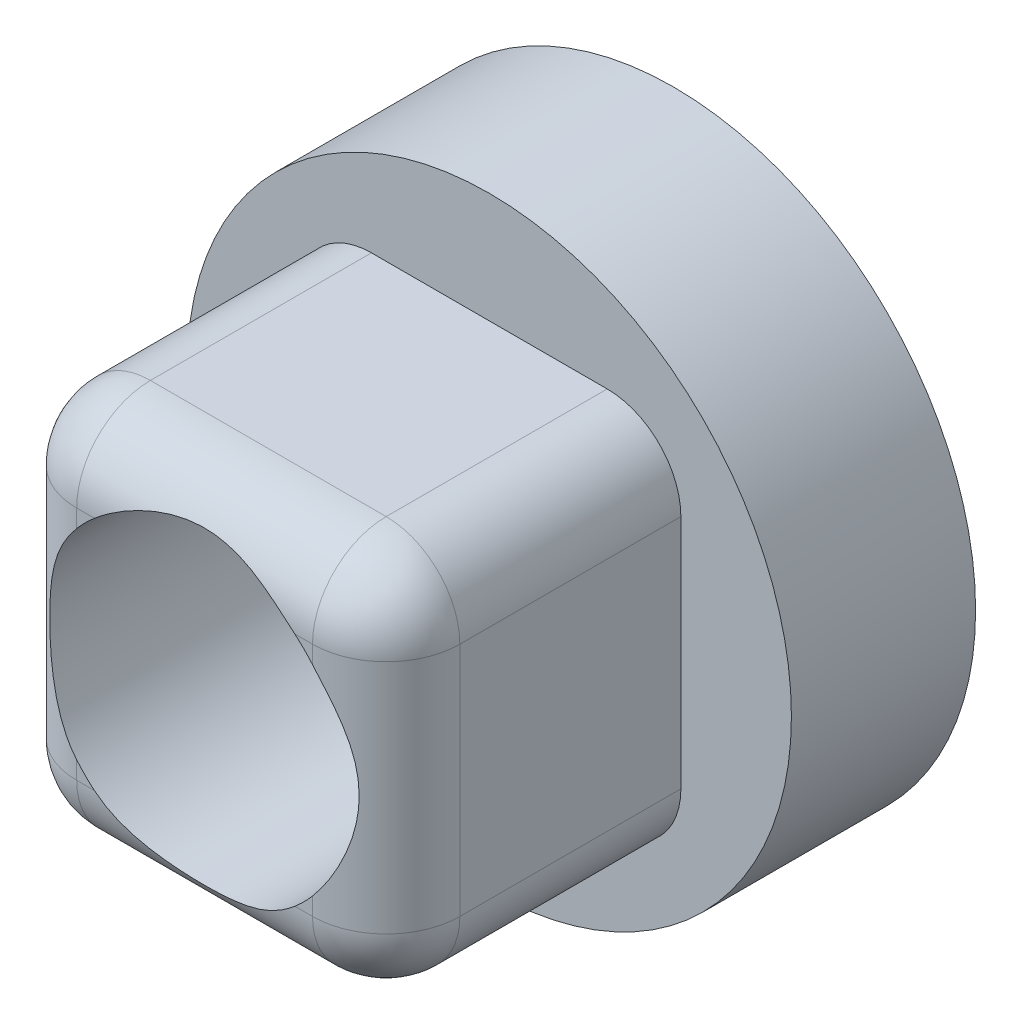
SolidWorks part; units mm, degrees
ref_plane "Front Plane" through (0, 0, 0) normal (1, 0, 0) x (0, 1, 0)
ref_plane "Top Plane" through (0, 0, 0) normal (0, 0, 1) x (0, 1, 0)
ref_plane "Right Plane" through (0, 0, 0) normal (0, 1, 0) x (-1, 0, 0)
sketch "Sketch1" plane through (0, 0, 0) normal (0, 0, 1) x (0, 1, 0)
  circle A1 centre (0, 0) radius 4.1
  dimension "8.2" = 8.2
extrude "Boss-Extrude1" add sketch "Sketch1" along normal blind 2.5
sketch "Sketch2" plane through (0, 0, 2.5) normal (0, 0, 1) x (1, 0, 0)
  line L1 (-2.6, -2.6) -> (2.6, -2.6)
  line L2 (-2.6, -2.6) -> (-2.6, 2.6)
  line L3 (-2.6, 2.6) -> (2.6, 2.6)
  line L4 (2.6, -2.6) -> (2.6, 2.6)
  line L5 (-2.6, -2.6) -> (2.6, 2.6) construction
  line L6 (-2.6, 2.6) -> (2.6, -2.6) construction
  point P0 (0, 0)
  dimension "D1" = 5.2
extrude "Boss-Extrude2" add sketch "Sketch2" along normal blind 4
sketch "Sketch3" plane through (0, 0, 6.5) normal (0, 0, 1) x (1, 0, 0)
  circle A0 centre (0, 0) radius 2.1
extrude "Cut-Extrude1" cut sketch "Sketch3" against normal through all
fillet "Fillet1" radius 1 8 edges at (2.6, 0, 6.5) (0, -2.6, 6.5) (-2.6, 0, 6.5) (0, 2.6, 6.5) (-2.6, 2.6, 4.5) (2.6, 2.6, 4.5) (2.6, -2.6, 4.5) (-2.6, -2.6, 4.5)
